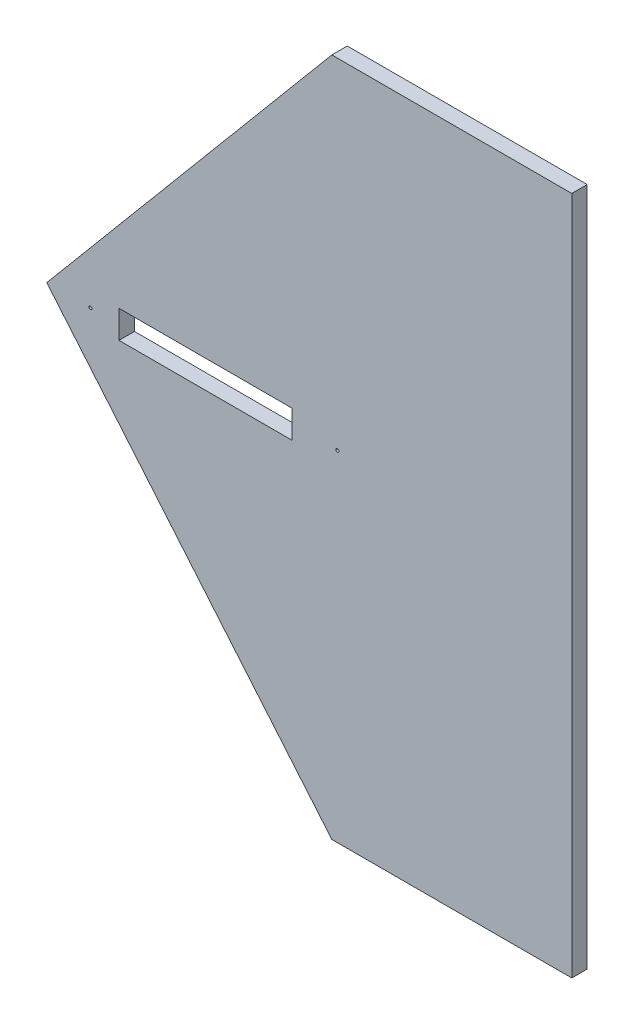
SolidWorks part; units mm, degrees
material "Carbon/Foam Panel"
ref_plane "Front Plane" through (0, 0, 0) normal (0, 0, 1) x (1, 0, 0)
ref_plane "Top Plane" through (0, 0, 0) normal (0, 1, 0) x (1, 0, 0)
ref_plane "Right Plane" through (0, 0, 0) normal (1, 0, 0) x (0, 0, -1)
sketch "Sketch1" plane through (0, 0, 0) normal (0, 0, 1) x (1, 0, 0)
  line L0 (215.9, 139.7) -> (215.9, -139.7)
  line L1 (215.9, -139.7) -> (117.2222, -139.7)
  line L2 (117.2222, -139.7) -> (0, 0)
  line L3 (0, 0) -> (117.2222, 139.7)
  line L4 (117.2222, 139.7) -> (215.9, 139.7)
  line L5 (117.2222, 139.7) -> (117.2222, -139.7) construction
  line L6 (0, 0) -> (215.9, 0) construction
  point P2 (117.2222, 0)
  dimension "D1" = 279.4
  dimension "D2" = 50
  dimension "D3" = 98.6778
  dimension "D4" = 215.9
extrude "Boss-Extrude1" add sketch "Sketch1" along normal blind 6.35
sketch "Sketch4" plane through (0, 0, 0) normal (0, 0, 1) x (1, 0, 0)
  line L1 (29.718, 5.715) -> (100.838, 5.715)
  line L2 (29.718, 5.715) -> (29.718, -5.715)
  line L3 (29.718, -5.715) -> (100.838, -5.715)
  line L4 (100.838, 5.715) -> (100.838, -5.715)
  line L5 (100.838, 0) -> (29.718, 0) construction
  line L6 (65.278, 5.715) -> (65.278, -5.715) construction
  line L7 (3.4925, 0) -> (-3.4925, 0) construction
  line L8 (32.258, 5.715) -> (32.258, -5.715) construction
  dimension "D1" = 2.54
  dimension "D2" = 68.58
  dimension "D3" = 11.43
  dimension "D4" = 29.718
extrude "Cut-Extrude1" cut sketch "Sketch4" along normal through all
sketch "Sketch5" plane through (0, 0, 0) normal (0, 0, 1) x (1, 0, 0)
  line L2 (17.9578, 0) -> (119.5578, 0) construction
  line L3 (29.718, 5.715) -> (29.718, -5.715) construction
  circle A0 centre (17.9578, 0) radius 0.635
  circle A1 centre (119.5578, 0) radius 0.635
  point P4 (29.718, 0)
  point P5 (29.718, 0)
  dimension "D1" = 1.27
  dimension "D3" = 1.27
  dimension "D2" = 101.6
  dimension "D4" = 11.7602
extrude "Cut-Extrude2" cut sketch "Sketch5" along normal through all
equation "\"D3@Sketch5\"=\"D1@Sketch5\""
